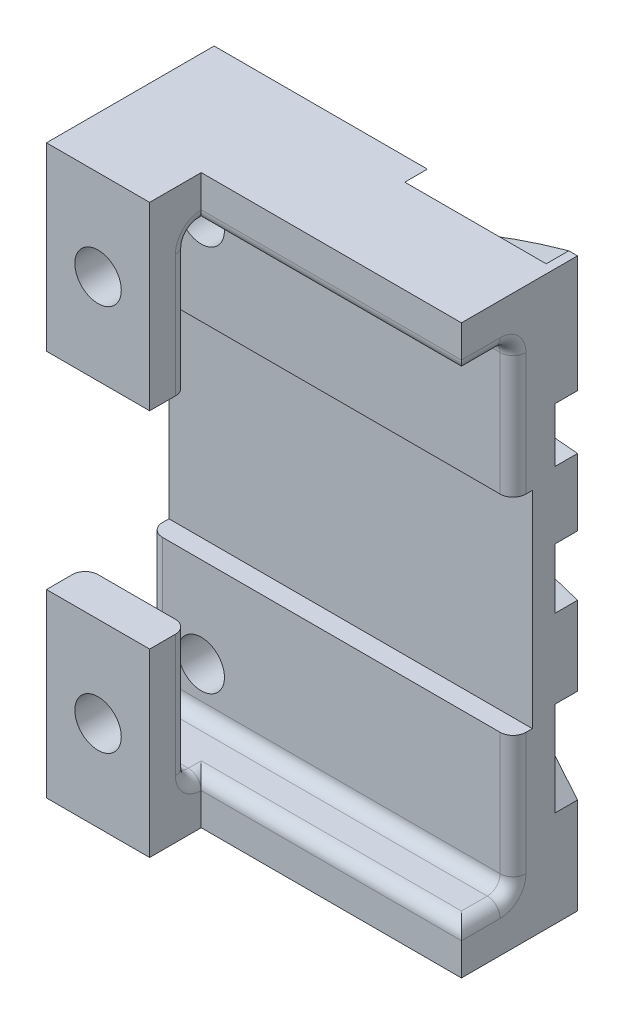
SolidWorks part; units mm, degrees
ref_plane "Front Plane" through (0, 0, 0) normal (0, 0, 1) x (1, 0, 0)
ref_plane "Top Plane" through (0, 0, 0) normal (0, 1, 0) x (1, 0, 0)
ref_plane "Right Plane" through (0, 0, 0) normal (1, 0, 0) x (0, 0, -1)
sketch "Sketch1" plane through (0, 0, 0) normal (0, 0, 1) x (1, 0, 0)
  line L1 (-14.09, -22) -> (14.09, -22)
  line L2 (-14.09, -22) -> (-14.09, 22)
  line L3 (-14.09, 22) -> (14.09, 22)
  line L4 (14.09, -22) -> (14.09, 22)
  line L5 (-14.09, -22) -> (14.09, 22) construction
  line L6 (-14.09, 22) -> (14.09, -22) construction
  point P0 (0, 0)
  dimension "D1" = 44
  dimension "D2" = 28.18
extrude "Boss-Extrude1" add sketch "Sketch1" along normal blind 11 and the other way blind 2
sketch "Sketch3" plane through (-14.09, 0, 0) normal (-1, 0, 0) x (0, 0, 1)
  line L0 (8, 8) -> (11, 8)
  line L5 (8, 18.5) -> (3, 18.5)
  line L6 (8, 18.5) -> (8, 8)
  line L7 (8, -18.5) -> (3, -18.5)
  line L8 (3, 18.5) -> (3, 8)
  line L9 (11, -8) -> (8, -8)
  line L10 (8, -8) -> (8, -18.5)
  line L13 (3, -8) -> (1.5034, -8)
  line L14 (11, 8) -> (11, -8)
  line L15 (14.8907, 0) -> (-5.9971, 0) construction
  line L16 (3, 8) -> (1.5034, 8)
  line L17 (1.5034, 8) -> (1.5034, -8)
  line L18 (3, -8) -> (3, -18.5)
  dimension "D1" = 3
  dimension "D2" = 5
  dimension "D3" = 37
extrude "Cut-Extrude1" cut sketch "Sketch3" against normal blind 37
sketch "Sketch4" plane through (0, -22, 0) normal (0, -1, 0) x (1, 0, 0)
  line L0 (-14.09, 11) -> (14.09, 11) construction
  line L1 (-6.09, 11) -> (14.09, 11)
  line L2 (-6.09, 11) -> (-6.09, 7)
  line L3 (-6.09, 7) -> (14.09, 7)
  line L4 (14.09, 11) -> (14.09, 7)
  line L5 (14.09, -2) -> (14.09, 11) construction
  line L6 (-14.09, -2) -> (-14.09, 11) construction
  dimension "D1" = 4
  dimension "D2" = 8
extrude "Cut-Extrude2" cut sketch "Sketch4" against normal blind 48
sketch "Sketch5" plane through (0, 0, -2) normal (0, 0, -1) x (-1, 0, 0)
  line L0 (14.09, 4.4317) -> (14.09, 4.2995)
  line L1 (-14.09, 22) -> (14.09, 22) construction
  line L2 (-2.4482, 22) -> (-13.4131, 22)
  line L3 (14.09, 4.4317) -> (14.09, 4.2995)
  line L4 (5.5922, -22) -> (0.0012, -22)
  line L5 (-14.09, 12.9435) -> (-14.09, 8.7272)
  line L6 (-2.4482, 22) -> (-13.4131, 22)
  line L7 (5.5922, -22) -> (0.0012, -22)
  line L8 (-5.5133, -22) -> (-9.4224, -22)
  line L9 (-14.09, 12.9435) -> (-14.09, 8.7272)
  line L10 (-14.09, 3.5233) -> (-14.09, -1.1313)
  line L11 (-14.09, -7.2405) -> (-14.09, -14.5457)
  line L12 (-5.5133, -22) -> (-9.4224, -22)
  line L13 (14.09, 22) -> (14.09, -22) construction
  line L14 (14.09, -22) -> (-14.09, -22) construction
  line L15 (-14.09, -22) -> (-14.09, 22) construction
  spline S0 degree 3 poles (-2.4482, 22) (19.5671, 11.5364) (5.1516, -7.6222) (5.5922, -22) knots 0 0 0 0 0.832841 0.832841 0.832841 0.832841
  spline S1 degree 3 poles (-13.4131, 22) (18.4961, 13.0475) (3.5462, -4.8632) (0.0012, -22) knots 0 0 0 0 0.886772 0.886772 0.886772 0.886772
  spline S2 degree 3 poles (-14.09, 12.9435) (17.0272, 14.2309) (-0.9132, -5.6377) (-5.5133, -22) knots 0 0 0 0 0.882154 0.882154 0.882154 0.882154
  spline S3 degree 3 poles (-14.09, 8.7272) (12.7104, 11.6786) (-5.2505, -7.0269) (-9.4224, -22) knots 0 0 0 0 0.871233 0.871233 0.871233 0.871233
  spline S4 degree 2 poles (-14.09, 3.5233) (7.9134, 11.6377) (-14.09, -14.5457) knots 0 0 0 1 1 1
  spline S5 degree 2 poles (-14.09, -1.1313) (-1.6541, 3.2119) (-14.09, -7.2405) knots 0 0 0 1 1 1
  line M1 (-14.09, 22) -> (-14.09, -22)
  line M2 (-14.09, -22) -> (14.09, -22)
  line M4 (14.09, 22) -> (-14.09, 22)
extrude "Cut-Extrude3" cut sketch "Sketch5" against normal blind 1.75 contours S3 S2 M1 M2 | S5 S4 M1 | S1 S0 M4 M2 region at (-9.2495, 2.4628, -2) region at (7.4678, -21.6069, -2) region at (4.526, -0.8216, -2)
sketch "Sketch7" plane through (0, 0, 11) normal (0, 0, 1) x (1, 0, 0)
  line L0 (-23.1576, 15) -> (2.9776, 15) construction
  line L1 (-6.09, 22) -> (-14.09, 22) construction
  line L2 (-14.09, 8) -> (-6.09, 8) construction
  line L3 (-31.6118, 0) -> (31.371, 0) construction
  line L4 (-10.09, 22.9416) -> (-10.09, 7.5663) construction
  line L5 (-6.09, 22) -> (-6.09, 8) construction
  line L6 (-14.09, 22) -> (-14.09, 8) construction
  circle A0 centre (-10.09, 15) radius 1.8
  circle A1 centre (-10.09, -15) radius 1.8
  point P15 (-10.09, 15)
  dimension "D1" = 3.6
extrude "Cut-Extrude4" cut sketch "Sketch7" against normal blind 23
fillet "Fillet1" radius 1 20 edges at (-14.09, -13.25, 3) (-14.09, -13.25, 8) (14.09, -13.25, 3) (-6.09, -13.25, 8) (14.09, 13.25, 3) (-14.09, 13.25, 3) (-14.09, 13.25, 8) (-6.09, 13.25, 8) (-14.09, -18.5, 5.5) (0, -18.5, 3) (14.09, -18.5, 5) (4, -18.5, 7) (-6.09, -18.5, 7.5) (-10.09, -18.5, 8) (14.09, 18.5, 5) (0, 18.5, 3) (-14.09, 18.5, 5.5) (-10.09, 18.5, 8) (-6.09, 18.5, 7.5) (4, 18.5, 7)
sketch "Sketch8" plane through (0, 0, -2) normal (0, 0, -1) x (-1, 0, 0)
  circle A0 centre (10.09, -15) radius 3.25
  circle A1 centre (10.09, 15) radius 3.25
  dimension "D1" = 6.5
extrude "Cut-Extrude5" cut sketch "Sketch8" against normal blind 1.75
